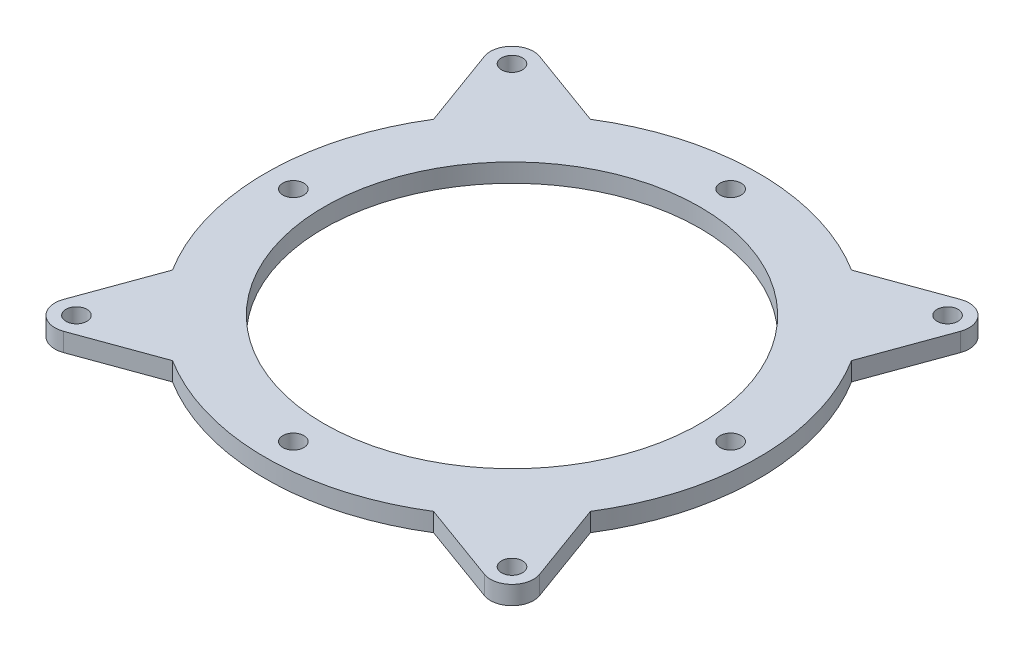
SolidWorks part; units mm, degrees
ref_plane "前视基准面" through (0, 0, 0) normal (0, 0, 1) x (1, 0, 0)
ref_plane "上视基准面" through (0, 0, 0) normal (0, 1, 0) x (1, 0, 0)
ref_plane "右视基准面" through (0, 0, 0) normal (1, 0, 0) x (0, 0, -1)
sketch "草图1" plane through (0, 0, 0) normal (0, 1, 0) x (1, 0, 0)
  line L0 (0, 35.5) -> (0, 0) construction
  line L1 (0, 0) -> (35.5, 0) construction
  line L2 (34.1583, 38.6443) -> (21.192, 33.9249)
  line L3 (-35.3553, -35.3553) -> (35.3553, 35.3553) construction
  line L4 (38.6443, 34.1583) -> (33.9249, 21.192)
  line L5 (34.1583, -38.6443) -> (21.192, -33.9249)
  line L6 (38.6443, -34.1583) -> (33.9249, -21.192)
  line L7 (-38.6443, -34.1583) -> (-33.9249, -21.192)
  line L8 (-34.1583, -38.6443) -> (-21.192, -33.9249)
  line L9 (-34.1583, 38.6443) -> (-21.192, 33.9249)
  line L10 (-38.6443, 34.1583) -> (-33.9249, 21.192)
  circle A0 centre (0, 0) radius 30.5
  arc A1 (-21.192, -33.9249) -> (21.192, -33.9249) centre (0, 0) ccw
  circle A2 centre (0, 0) radius 35.5 construction
  circle A3 centre (0, 35.5) radius 1.7
  circle A4 centre (35.5, 0) radius 1.7
  circle A5 centre (0, -35.5) radius 1.7
  circle A6 centre (-35.5, 0) radius 1.7
  circle A7 centre (35.3553, 35.3553) radius 1.7
  arc A8 (38.6443, 34.1583) -> (34.1583, 38.6443) centre (35.3553, 35.3553) ccw
  arc A9 (34.1583, -38.6443) -> (38.6443, -34.1583) centre (35.3553, -35.3553) ccw
  circle A10 centre (35.3553, -35.3553) radius 1.7
  arc A11 (-38.6443, -34.1583) -> (-34.1583, -38.6443) centre (-35.3553, -35.3553) ccw
  circle A12 centre (-35.3553, -35.3553) radius 1.7
  arc A13 (-34.1583, 38.6443) -> (-38.6443, 34.1583) centre (-35.3553, 35.3553) ccw
  circle A14 centre (-35.3553, 35.3553) radius 1.7
  circle A15 centre (0, 0) radius 40 construction
  arc A16 (33.9249, -21.192) -> (33.9249, 21.192) centre (0, 0) ccw
  arc A17 (21.192, 33.9249) -> (-21.192, 33.9249) centre (0, 0) ccw
  arc A18 (-33.9249, 21.192) -> (-33.9249, -21.192) centre (0, 0) ccw
  point P18 (0, 0)
  point P47 (0, 0)
  dimension "D1" = 4.5
  dimension "D2" = 80
  dimension "D3" = 5
  dimension "D4" = 3.4
  dimension "D8" = 100
  dimension "D9" = 25
  dimension "D10" = 3.4
  dimension "D7" = 7
  dimension "D6" = 45
  dimension "D5" = 4
  dimension "D11" = 4
extrude "凸台-拉伸1" add sketch "草图1" along normal blind 3
